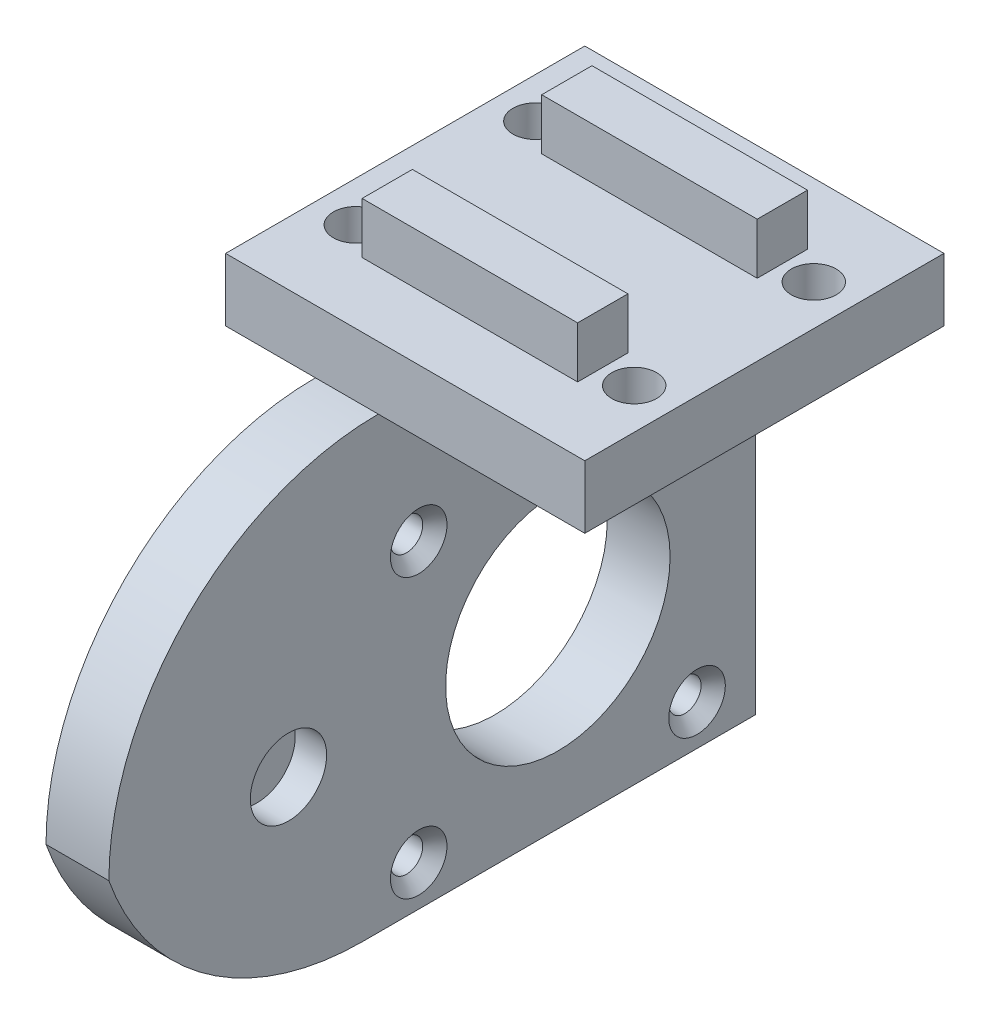
SolidWorks part; units mm, degrees
ref_plane "Alzado" through (0, 0, 0) normal (0, 0, 1) x (1, 0, 0)
ref_plane "Planta" through (0, 0, 0) normal (0, 1, 0) x (1, 0, 0)
ref_plane "Vista lateral" through (0, 0, 0) normal (1, 0, 0) x (0, 0, -1)
sketch "Croquis1" plane through (0, 0, 0) normal (0, 1, 0) x (1, 0, 0)
  line L1 (20, 20) -> (-20, 20)
  line L2 (20, 20) -> (20, -20)
  line L3 (20, -20) -> (-20, -20)
  line L4 (-20, 20) -> (-20, -20)
  line L5 (20, 20) -> (-20, -20) construction
  line L6 (20, -20) -> (-20, 20) construction
  point P0 (0, 0)
  dimension "D1" = 40
  dimension "D2" = 40
extrude "Saliente-Extruir1" add sketch "Croquis1" along normal blind 7
sketch "Croquis3" plane through (-20, 0, 0) normal (-1, 0, 0) x (0, 0, 1)
  line L0 (-20, 7) -> (20, 7) construction
  line L5 (-12.8, 12.7) -> (-7.2, 7) construction
  line L6 (7.2, 7) -> (12.8, 7)
  line L7 (7.2, 7) -> (7.2, 12.7)
  line L8 (7.2, 12.7) -> (12.8, 12.7)
  line L9 (12.8, 7) -> (12.8, 12.7)
  line L12 (-7.2, 7) -> (-12.8, 7)
  line L13 (-7.2, 7) -> (-7.2, 12.7)
  line L14 (-7.2, 12.7) -> (-12.8, 12.7)
  line L15 (-12.8, 7) -> (-12.8, 12.7)
  line L16 (-7.2, 12.7) -> (-12.8, 7) construction
  line L17 (7.2, 12.7) -> (12.8, 7) construction
  line L18 (12.8, 12.7) -> (7.2, 7) construction
  point P10 (-10, 9.85)
  point P11 (10, 9.85)
  dimension "D1" = 10
  dimension "D2" = 10
  dimension "D3" = 5.6
  dimension "D4" = 5.6
  dimension "D5" = 5.7
extrude "Saliente-Extruir3" add sketch "Croquis3" against normal up to surface (40 mm away) up to face at (20, 3.5, 0)
sketch "Croquis19" plane through (0, 12.7, 0) normal (0, 1, 0) x (1, 0, 0)
  line L0 (20, 20) -> (-20, 20) construction
  line L1 (-12, 20) -> (-20, 20)
  line L2 (-12, 20) -> (-12, -20)
  line L3 (-12, -20) -> (-20, -20)
  line L4 (-20, 20) -> (-20, -20)
  line L5 (-12, 20) -> (-20, -20) construction
  line L6 (-12, -20) -> (-20, 20) construction
  line L7 (20, 20) -> (12, 20)
  line L8 (20, 20) -> (20, -20)
  line L9 (20, -20) -> (12, -20)
  line L10 (12, 20) -> (12, -20)
  line L11 (20, 20) -> (12, -20) construction
  line L12 (20, -20) -> (12, 20) construction
  line L13 (-20, -20) -> (20, -20) construction
  line L16 (20, -7.2) -> (20, 7.2) construction
  line L17 (-20, 7.2) -> (-20, -7.2) construction
  point P0 (-16, 0)
  point P5 (16, 0)
  dimension "D1" = 8
  dimension "D4" = 8
extrude "Cortar-Extruir5" cut sketch "Croquis19" against normal up to surface (5.7 mm away) up to face at (0, 7, 0)
sketch "Croquis20" plane through (0, 7, 0) normal (0, 1, 0) x (1, 0, 0)
  line L0 (15.5, 16.9883) -> (15.5, -23.2433) construction
  line L3 (20, 20) -> (-20, 20) construction
  line L4 (-20, -20) -> (20, -20) construction
  line L5 (-15.5, 16.9883) -> (-15.5, -23.2433) construction
  line L6 (20, -20) -> (20, 20) construction
  line L7 (-20, 20) -> (-20, -20) construction
  circle A0 centre (-15.5, 10) radius 2.5
  circle A1 centre (15.5, 10) radius 2.5
  circle A2 centre (15.5, -10) radius 2.5
  circle A3 centre (-15.5, -10) radius 2.5
  dimension "D1" = 5
  dimension "D2" = 10
  dimension "D3" = 10
  dimension "D4" = 4.5
  dimension "D5" = 4.5
extrude "Cortar-Extruir6" cut sketch "Croquis20" against normal up to surface (7 mm away) up to face at (0, 0, 0)
sketch "Croquis21" plane through (0, 0, 0) normal (0, -1, 0) x (1, 0, 0)
  line L0 (-20, 20) -> (20, 20) construction
  line L9 (-20, -20) -> (-20, 20) construction
  line L10 (-3, 50) -> (-10, 50)
  line L11 (-3, 50) -> (-3, -22)
  line L12 (-3, -22) -> (-10, -22)
  line L13 (-10, 50) -> (-10, -22)
  line L14 (-3, 50) -> (-10, -22) construction
  line L15 (-3, -22) -> (-10, 50) construction
  point P0 (0, 0)
  point P1 (-6.5, 14)
  dimension "D1" = 7
  dimension "D2" = 72
  dimension "D3" = 30
  dimension "D4" = 10
extrude "Saliente-Extruir4" add sketch "Croquis21" along normal blind 50
sketch "Croquis22" plane through (-3, 0, 0) normal (1, 0, 0) x (0, 0, -1)
  line L0 (20, 0) -> (-20, 0) construction
  line L1 (22, -50) -> (-50, -50) construction
  circle A0 centre (0, -30) radius 12.5
  point P5 (0, 0)
  dimension "D1" = 25
  dimension "D2" = 20
extrude "Cortar-Extruir7" cut sketch "Croquis22" against normal up to surface (7 mm away) up to face at (-10, -16.6667, 9.3333)
sketch "Croquis23" plane through (-3, 0, 0) normal (1, 0, 0) x (0, 0, -1)
  line L1 (15.5, -14.5) -> (-15.5, -14.5) construction
  line L2 (15.5, -14.5) -> (15.5, -45.5) construction
  line L3 (15.5, -45.5) -> (-15.5, -45.5) construction
  line L4 (-15.5, -14.5) -> (-15.5, -45.5) construction
  line L5 (15.5, -14.5) -> (-15.5, -45.5) construction
  line L6 (15.5, -45.5) -> (-15.5, -14.5) construction
  point P0 (0, -30)
  dimension "D1" = 31
  dimension "D2" = 31
hole_wizard "Avellanado para tornillo con cabeza plana de M31" positions "Croquis3D1" profile "Croquis24" countersink size "M3" standard "Ansi Metric" end condition through all
sketch3d "Croquis3D1"
  point P0 (-3, -14.5, 15.5)
  point P3 (-3, -14.5, -15.5)
  point P6 (-3, -45.5, -15.5)
  point P9 (-3, -45.5, 15.5)
sketch "Croquis24" plane through (-3, -14.5, 15.5) normal (0, 1, 0) x (0, 0, -1)
  line L0 (0, 0) -> (0, 17)
  line L1 (0, 17) -> (1.8, 17)
  line L2 (1.8, 17) -> (1.8, 1.35)
  line L3 (1.8, 1.35) -> (3.15, 0)
  line L5 (3.15, 0) -> (0, 0)
  line L6 (-1.8, 1.35) -> (-3.15, 0) construction
  line L11 (0, -6.35) -> (0, 107.95) construction
  dimension "Diámetro de taladro hasta el siguiente" = 3.6
  dimension "Profundidad de taladro hasta el siguiente" = 17
  dimension "Diámetro de avellanado cercano" = 6.3
  dimension "Ángulo de avellanado cercano" = 90
sketch "Croquis25" plane through (-3, 0, 0) normal (1, 0, 0) x (0, 0, -1)
  circle A0 centre (-30, -30) radius 4.25
  dimension "D2" = 8.5
  dimension "D1" = 30
extrude "Cortar-Extruir8" cut sketch "Croquis25" against normal blind 3.5
fillet "Redondeo1" radius 30 1 edges at (-6.5, 0, 50)
fillet "Redondeo2" radius 30 1 edges at (-6.5, -50, 50)
